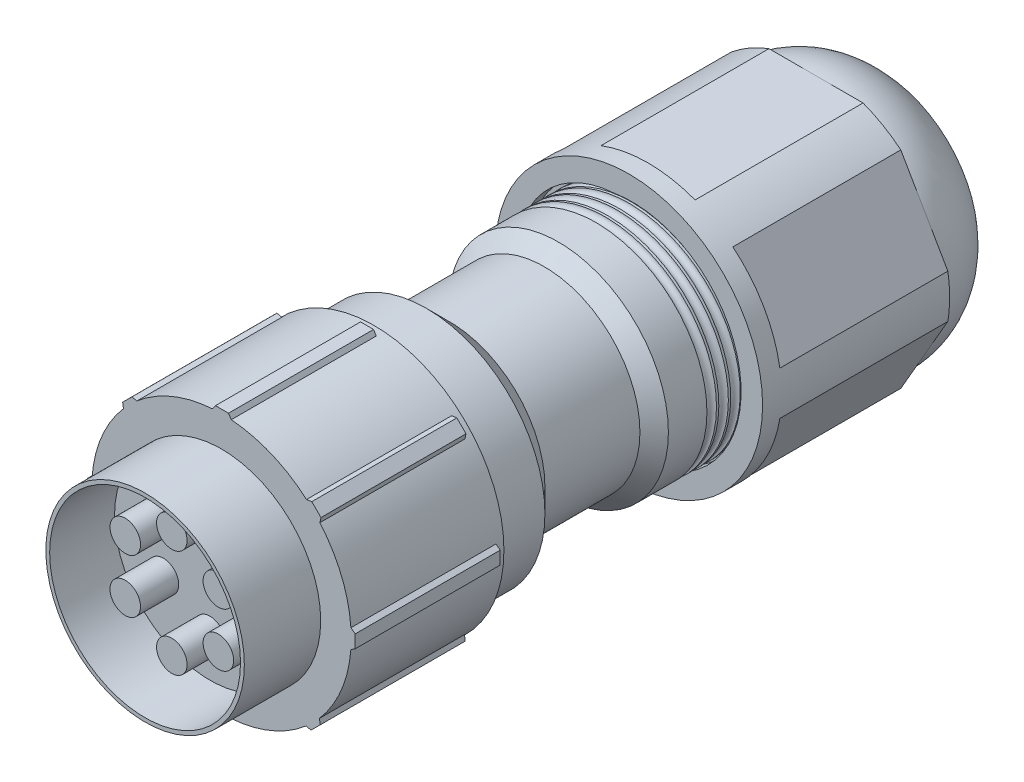
SolidWorks part; units mm, degrees
ref_plane "Front Plane" through (0, 0, 0) normal (0, 0, 1) x (1, 0, 0)
ref_plane "Top Plane" through (0, 0, 0) normal (0, 1, 0) x (1, 0, 0)
ref_plane "Right Plane" through (0, 0, 0) normal (1, 0, 0) x (0, 0, -1)
sketch "Sketch1" plane through (0, 0, 0) normal (0, 0, 1) x (1, 0, 0)
  circle A0 centre (0, 0) radius 8.5
  dimension "D1" = 17
extrude "Boss-Extrude1" add sketch "Sketch1" against normal blind 10
sketch "Sketch2" plane through (0, 0, 0) normal (0, 0, 1) x (1, 0, 0)
  circle A0 centre (0, 0) radius 6.5
  dimension "D1" = 13
extrude "Boss-Extrude2" add sketch "Sketch2" along normal blind 5
sketch "Sketch3" plane through (0, 0, 0) normal (1, 0, 0) x (0, 0, -1)
  line L0 (10, 7.7662) -> (13.4193, 7.7662)
  line L2 (10, -8.5) -> (10, 8.5) construction
  line L3 (13.4193, 7.7662) -> (14.9223, 6.2632)
  line L4 (14.9223, 6.2632) -> (21.1445, 6.2632)
  line L5 (21.1445, 6.2632) -> (22.0763, 7.195)
  line L6 (22.0763, 7.195) -> (23.94, 7.195)
  line L7 (23.94, 7.195) -> (23.94, 0)
  line L8 (23.94, 0) -> (10, 0)
  line L9 (10, 0) -> (10, 7.7662)
revolve "Revolve1" add sketch "Sketch3" angle 360 about L8
sketch "Sketch4" plane through (0, 0, -23.94) normal (0, 0, -1) x (-1, 0, 0)
  circle A0 centre (0, 0) radius 7.195
extrude "Boss-Extrude3" add sketch "Sketch4" along normal blind 3.5
sketch "Sketch5" plane through (0, 0, -27.44) normal (0, 0, -1) x (-1, 0, 0)
  circle A0 centre (0, 0) radius 7.195 construction
  circle A1 centre (0, 0) radius 7.195
curve "Helix/Spiral1" pitch 0.7778 height 3.5 turns 4.5
sketch "Sketch6" plane through (0, 0, 0) normal (1, 0, 0) x (0, 0, -1)
  circle A1 centre (27.44, -7.195) radius 0.3122
sweep "Cut-Sweep2" cut profiles "Sketch6" path "Helix/Spiral1"
sketch "Sketch7" plane through (0, 0, -27.44) normal (0, 0, -1) x (-1, 0, 0)
  circle A0 centre (0, 0) radius 8.75
  dimension "D1" = 17.5
extrude "Boss-Extrude5" add sketch "Sketch7" along normal blind 11.5
sketch "Sketch8" plane through (0, 0, 0) normal (1, 0, 0) x (0, 0, -1)
  line L0 (38.94, -8.75) -> (38.94, 8.75) construction
  line L2 (38.94, 0) -> (38.94, 8.1909)
  line L4 (41.9978, 0) -> (38.94, 0)
  line L5 (43.1551, 6.3625) -> (43.1551, 0)
  line L6 (43.1551, 0) -> (41.9978, 0)
  arc A0 (38.94, 8.1909) -> (43.1551, 6.3625) centre (39.249, 3.1304) cw
revolve "Revolve3" add sketch "Sketch8" angle 360 about L4
sketch "Sketch10" plane through (0, 0, -43.1551) normal (0, 0, -1) x (-1, 0, 0)
  circle A0 centre (0, 0) radius 3
  dimension "D1" = 6
extrude "Cut-Extrude1" cut sketch "Sketch10" against normal blind 3
sketch "Sketch11" plane through (0, 0, 5) normal (0, 0, 1) x (1, 0, 0)
  circle A0 centre (0, 0) radius 6.25
  dimension "D1" = 12.5
extrude "Cut-Extrude2" cut sketch "Sketch11" against normal blind 4.25
sketch "Sketch12" plane through (0, 0, 0.75) normal (0, 0, 1) x (1, 0, 0)
  circle A1 centre (0, 3.43) radius 1
  point P6 (0, 0)
  dimension "D2" = 2
extrude "Boss-Extrude6" add sketch "Sketch12" along normal blind 2.5
sketch "Sketch14" plane through (0, 0, 0) normal (0, 0, 1) x (1, 0, 0)
  line L10 (0.0229, 8.5) -> (0.0229, 8.4712)
  line L11 (0.0229, 8.4712) -> (0.6429, 8.4757)
  line L12 (0.0229, 8.4712) -> (-0.5971, 8.479)
  line L13 (-0.5971, 8.479) -> (-0.3883, 8.759)
  line L14 (0.6429, 8.4757) -> (0.4618, 8.7557)
  line L15 (-0.3883, 8.759) -> (0.4618, 8.7557)
  circle A3 centre (0, 0) radius 8.5 construction
  dimension "D1" = 0.62
  dimension "D2" = 0.62
  dimension "D3" = 0.28
  dimension "D4" = 0.28
pattern_circular "CirPattern4" count 6 over 360 about axis through (0, -0.0901, 0) along (0, 0, 1) of "Boss-Extrude6"
extrude "Boss-Extrude7" add sketch "Sketch14" against normal blind 9.5
pattern_circular "CirPattern2" count 8 over 360 about axis through (0, 0, 0) along (0, 0, 1) of "Boss-Extrude7"
sketch "Sketch15" plane through (0, 0, -27.44) normal (0, 0, 1) x (1, 0, 0)
  arc A0 (-0.9885, 8.694) -> (-8.75, 0) centre (0, 0) ccw
  circle A1 centre (0, 0) radius 8.75 construction
  arc A2 (-8.75, 0) -> (-0.3082, -8.7446) centre (0, 0) ccw
  arc A3 (8.75, 0) -> (-0.3082, -8.7446) centre (0, 0) cw
  arc A4 (8.75, 0) -> (-0.9885, 8.694) centre (0, 0) ccw
  arc A5 (-0.9885, 7.1742) -> (-7.2763, 0) centre (-0.5453, 0.4432) ccw
  arc A6 (-7.2763, 0) -> (-2.2166, -7.0118) centre (-0.132, -0.1761) ccw
  arc A7 (-2.2166, -7.0118) -> (7.0803, 2.028) centre (-0.0575, 0.0683) ccw
  arc A8 (7.0803, 2.028) -> (-0.9885, 7.1742) centre (0.2001, 0.139) ccw
extrude "Boss-Extrude8" add sketch "Sketch15" along normal blind 0.75
sketch "Sketch16" plane through (0, 0, -38.94) normal (0, 0, -1) x (-1, 0, 0)
  line L0 (-0.0296, 8.8518) -> (-3.5296, 8.8518)
  line L1 (-3.5296, 8.8518) -> (-3.5296, 8.1896)
  line L2 (-0.0296, 8.8518) -> (3.4704, 8.8518)
  line L3 (-3.5296, 8.1896) -> (3.4704, 8.1896)
  line L4 (3.4704, 8.1896) -> (3.4704, 8.8518)
  dimension "D1" = 3.5
  dimension "D2" = 3.5
  dimension "D3" = 7
extrude "Cut-Extrude3" cut sketch "Sketch16" against normal blind 11
pattern_circular "CirPattern3" count 6 over 360 about axis through (0, 0, 0) along (0, 0, 1) of "Cut-Extrude3"
